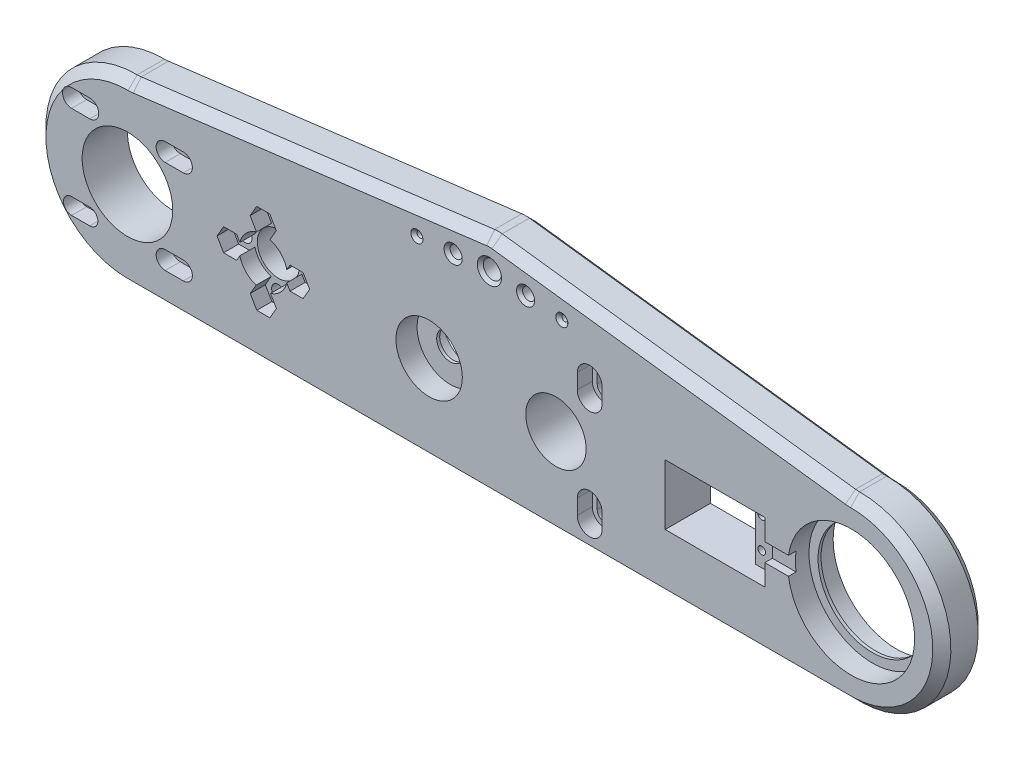
SolidWorks part; units mm, degrees
material "PLA+"
ref_plane "Front Plane" through (0, 0, 0) normal (0, 0, 1) x (1, 0, 0)
ref_plane "Top Plane" through (0, 0, 0) normal (0, 1, 0) x (1, 0, 0)
ref_plane "Right Plane" through (0, 0, 0) normal (1, 0, 0) x (0, 0, -1)
sketch "Sketch1" plane through (0, 0, 0) normal (0, 0, 1) x (1, 0, 0)
  line L2 (203.08, 10) -> (203.08, -10)
  line L6 (178.08, -10) -> (211.08, -10)
  line L7 (178.08, -10) -> (178.08, 10)
  line L8 (211.08, 10) -> (178.08, 10)
  line L11 (150.58, 20.5) -> (150.58, 15.5)
  line L12 (155.58, 15.5) -> (155.58, 20.5)
  line L13 (239.71, 0) -> (99.91, 0) construction
  line L17 (15.5, 15.5) -> (15.5, -15.5) construction
  line L18 (99.91, 0) -> (0, 0) construction
  line L19 (155.58, -15.5) -> (155.58, -20.5)
  line L20 (150.58, -20.5) -> (150.58, -15.5)
  line L22 (-15.5, -15.5) -> (15.5, -15.5) construction
  line L23 (-15.5, -15.5) -> (-15.5, 15.5) construction
  line L24 (-15.5, 15.5) -> (15.5, 15.5) construction
  line L25 (15.5, -15.5) -> (15.5, 15.5) construction
  line L26 (-15.5, -15.5) -> (15.5, 15.5) construction
  line L27 (-15.5, 15.5) -> (15.5, -15.5) construction
  line L29 (211.08, 10) -> (213.08, 10)
  line L30 (213.08, 10) -> (213.08, -10)
  line L31 (213.08, -10) -> (211.08, -10)
  line L34 (0.8664, 29.9878) -> (238.8536, 29.9878)
  line L35 (-1.0627, -29.9815) -> (240.7645, -29.9815)
  circle A0 centre (239.71, 0) radius 21
  circle A1 centre (99.91, 0) radius 11
  circle A2 centre (0, 0) radius 15
  arc A3 (0.8664, 29.9878) -> (-1.0627, -29.9815) centre (0, 0) ccw
  arc A4 (240.7645, -29.9815) -> (238.8536, 29.9878) centre (239.71, 0) ccw
  circle A6 centre (205.08, 5) radius 1.25
  circle A7 centre (205.08, -5) radius 1.25
  arc A13 (150.58, 15.5) -> (155.58, 15.5) centre (153.08, 15.5) ccw
  arc A14 (155.58, 20.5) -> (150.58, 20.5) centre (153.08, 20.5) ccw
  circle A15 centre (99.91, 0) radius 4
  circle A17 centre (-15.5, -15.5) radius 1.5
  circle A18 centre (-15.5, 15.5) radius 1.5
  circle A19 centre (45, -11) radius 2.25
  circle A20 centre (56, 0) radius 2.25
  circle A21 centre (34, 0) radius 2.25
  circle A22 centre (15.5, -15.5) radius 1.5
  circle A23 centre (15.5, 15.5) radius 1.5
  circle A24 centre (45, 11) radius 2.25
  circle A25 centre (45, 0) radius 7
  circle A26 centre (45, 0) radius 11 construction
  arc A28 (155.58, -20.5) -> (150.58, -20.5) centre (153.08, -20.5) cw
  arc A29 (150.58, -15.5) -> (155.58, -15.5) centre (153.08, -15.5) cw
  circle A30 centre (239.71, 0) radius 17
  circle A31 centre (0, 0) radius 11
  dimension "D5" = 3
  dimension "D6" = 14
  dimension "D7" = 22
  dimension "D8" = 2
  dimension "D10" = 8
  dimension "D11" = 22
  dimension "D12" = 2.5
  dimension "D14" = 8
  dimension "D20" = 4.5
  dimension "D24" = 42
  dimension "D25" = 30
  dimension "D30" = 15.5
  dimension "D32" = 4
  dimension "D33" = 4
  dimension "D34" = 30
  dimension "D35" = 22
  dimension "D3" = 31
  dimension "D4" = 31
  dimension "D9" = 45
  dimension "D13" = 5
  dimension "D17" = 33
  dimension "D18" = 20
  dimension "D21" = 10
  dimension "D22" = 5
  dimension "D26" = 99.91
  dimension "D27" = 139.8
  dimension "D36" = 31
sketch "Sketch2" plane through (0, 0, 0) normal (0, 0, 1) x (1, 0, 0)
  line L0 (178.08, -10) -> (211.08, -10) construction
  line L1 (178.08, -10) -> (178.08, 10) construction
  line L2 (211.08, -10) -> (211.08, 10) construction
  line L3 (211.08, 10) -> (178.08, 10) construction
  line L4 (150.58, -20.5) -> (150.58, -15.5) construction
  line L5 (155.58, -15.5) -> (155.58, -20.5) construction
  line L6 (150.58, 20.5) -> (150.58, 15.5) construction
  line L7 (155.58, 15.5) -> (155.58, 20.5) construction
  line L10 (178.08, -10) -> (211.08, -10)
  line L11 (178.08, -10) -> (178.08, 10)
  line L12 (211.08, -10) -> (211.08, 10)
  line L13 (211.08, 10) -> (178.08, 10)
  line L14 (150.58, -20.5) -> (150.58, -15.5)
  line L15 (155.58, -15.5) -> (155.58, -20.5)
  line L16 (150.58, 20.5) -> (150.58, 15.5)
  line L17 (155.58, 15.5) -> (155.58, 20.5)
  line L18 (238.8536, 29.9878) -> (0.8664, 29.9878)
  line L19 (-1.0627, -29.9815) -> (240.7645, -29.9815)
  line L21 (-18.5, 15.5) -> (-12.5, 15.5) construction
  line L22 (-18.5, 17.3) -> (-12.5, 17.3)
  line L23 (-18.5, 13.7) -> (-12.5, 13.7)
  line L24 (12.5, 15.5) -> (18.5, 15.5) construction
  line L25 (12.5, 17.3) -> (18.5, 17.3)
  line L26 (12.5, 13.7) -> (18.5, 13.7)
  line L27 (-18.5, -15.5) -> (-12.5, -15.5) construction
  line L28 (-18.5, -13.7) -> (-12.5, -13.7)
  line L29 (-18.5, -17.3) -> (-12.5, -17.3)
  line L30 (12.5, -15.5) -> (18.5, -15.5) construction
  line L31 (12.5, -13.7) -> (18.5, -13.7)
  line L32 (12.5, -17.3) -> (18.5, -17.3)
  arc A0 (240.7645, -29.9815) -> (238.8536, 29.9878) centre (239.71, 0) ccw construction
  circle A1 centre (239.71, 0) radius 21 construction
  arc A2 (150.58, -20.5) -> (155.58, -20.5) centre (153.08, -20.5) ccw construction
  arc A3 (155.58, -15.5) -> (150.58, -15.5) centre (153.08, -15.5) ccw construction
  arc A4 (-18.5, 17.3) -> (-18.5, 13.7) centre (-18.5, 15.5) ccw
  arc A5 (-12.5, 13.7) -> (-12.5, 17.3) centre (-12.5, 15.5) ccw
  arc A6 (12.5, 17.3) -> (12.5, 13.7) centre (12.5, 15.5) ccw
  arc A7 (155.58, 20.5) -> (150.58, 20.5) centre (153.08, 20.5) ccw construction
  arc A8 (150.58, 15.5) -> (155.58, 15.5) centre (153.08, 15.5) ccw construction
  circle A9 centre (99.91, 0) radius 11 construction
  circle A11 centre (45, 0) radius 7 construction
  arc A15 (0.8664, 29.9878) -> (-1.0627, -29.9815) centre (0, 0) ccw construction
  circle A16 centre (-15.5, -15.5) radius 1.5 construction
  circle A17 centre (15.5, -15.5) radius 1.5 construction
  circle A18 centre (15.5, 15.5) radius 1.5 construction
  circle A19 centre (-15.5, 15.5) radius 1.5 construction
  circle A20 centre (0, 0) radius 15 construction
  arc A21 (240.7645, -29.9815) -> (238.8536, 29.9878) centre (239.71, 0) ccw
  circle A22 centre (239.71, 0) radius 21
  arc A23 (150.58, -20.5) -> (155.58, -20.5) centre (153.08, -20.5) ccw
  arc A24 (155.58, -15.5) -> (150.58, -15.5) centre (153.08, -15.5) ccw
  arc A28 (155.58, 20.5) -> (150.58, 20.5) centre (153.08, 20.5) ccw
  arc A29 (150.58, 15.5) -> (155.58, 15.5) centre (153.08, 15.5) ccw
  circle A30 centre (99.91, 0) radius 11
  circle A32 centre (45, 0) radius 7
  arc A36 (0.8664, 29.9878) -> (-1.0627, -29.9815) centre (0, 0) ccw
  circle A41 centre (0, 0) radius 15
  arc A42 (18.5, 13.7) -> (18.5, 17.3) centre (18.5, 15.5) ccw
  arc A43 (-18.5, -13.7) -> (-18.5, -17.3) centre (-18.5, -15.5) ccw
  arc A44 (-12.5, -17.3) -> (-12.5, -13.7) centre (-12.5, -15.5) ccw
  arc A45 (12.5, -13.7) -> (12.5, -17.3) centre (12.5, -15.5) ccw
  arc A46 (18.5, -17.3) -> (18.5, -13.7) centre (18.5, -15.5) ccw
  point P9 (-15.5, 15.5)
  point P23 (-15.5, 15.5)
  point P28 (15.5, 15.5)
  point P74 (-15.5, -15.5)
  point P81 (15.5, -15.5)
  dimension "D1" = 1.8
  dimension "D2" = 1.8
  dimension "D3" = 1.8
  dimension "D4" = 1.8
  dimension "D5" = 6
  dimension "D6" = 6
  dimension "D7" = 6
  dimension "D8" = 6
extrude "Boss-Extrude1" add sketch "Sketch2" along normal mid plane 15
sketch "Sketch3" plane through (0, 0, 0) normal (0, 0, 1) x (1, 0, 0)
  circle A0 centre (99.91, 0) radius 11 construction
  circle A4 centre (0, 0) radius 15 construction
  circle A6 centre (99.91, 0) radius 11
  circle A10 centre (0, 0) radius 15
  circle A12 centre (240.08, 0) radius 18
  circle A14 centre (99.91, 0) radius 4.5
  circle A15 centre (240.08, 0) radius 21.5
  dimension "D1" = 36
  dimension "D2" = 9
extrude "Boss-Extrude2" add sketch "Sketch3" along normal mid plane 1
sketch "Sketch4" plane through (0, 0, 0) normal (0, 0, 1) x (1, 0, 0)
  line L0 (211.08, -10) -> (211.08, 10) construction
  line L1 (203.08, 10) -> (203.08, -10) construction
  line L2 (211.08, -10) -> (211.08, 10)
  line L3 (203.08, 10) -> (203.08, -10)
  line L4 (203.08, 10) -> (211.08, 10)
  line L5 (203.08, -10) -> (211.08, -10)
  circle A0 centre (205.08, -5) radius 1.25 construction
  circle A1 centre (205.08, 5) radius 1.25 construction
  circle A2 centre (205.08, -5) radius 1.25
  circle A3 centre (205.08, 5) radius 1.25
extrude "Boss-Extrude3" add sketch "Sketch4" along normal mid plane 5
sketch "Sketch5" plane through (0, 0, 0) normal (0, 0, 1) x (1, 0, 0)
  line L0 (0.8664, 29.9878) -> (119.86, 44.9878)
  line L1 (119.86, 44.9878) -> (238.8536, 29.9878)
  line L2 (238.8536, 29.9878) -> (0.8664, 29.9878)
  line L3 (119.86, 30.9878) -> (95.86, 30.9878) construction
  line L4 (119.86, 44.9878) -> (119.86, 34.9878) construction
  circle A0 centre (119.86, 34.9878) radius 4
  circle A1 centre (107.86, 33.9878) radius 3
  circle A2 centre (95.86, 32.9878) radius 2
  circle A5 centre (131.86, 33.9878) radius 3
  circle A6 centre (143.86, 32.9878) radius 2
  point P18 (119.86, 29.9878)
  dimension "D2" = 8
  dimension "D3" = 6
  dimension "D4" = 4
  dimension "D1" = 15
  dimension "D5" = 12
  dimension "D6" = 12
  dimension "D7" = 10
extrude "Boss-Extrude6" add sketch "Sketch5" along normal mid plane 15 contours L2 L0 L1
fillet "Fillet1" radius 10 3 edges at (238.8536, 29.9878, 0) (0.8664, 29.9878, 0) (119.86, 44.9878, 0)
sketch "Sketch6" plane through (0, 0, 7.5) normal (0, 0, 1) x (1, 0, 0)
  circle A0 centre (131.86, 33.9878) radius 3 construction
  circle A1 centre (131.86, 33.9878) radius 3
  circle A2 centre (143.86, 32.9878) radius 2 construction
  circle A3 centre (143.86, 32.9878) radius 2
  circle A4 centre (95.86, 32.9878) radius 2 construction
  circle A15 centre (107.86, 33.9878) radius 3 construction
  circle A16 centre (119.86, 34.9878) radius 4 construction
  circle A17 centre (95.86, 32.9878) radius 2
  circle A18 centre (107.86, 33.9878) radius 3
  circle A19 centre (119.86, 34.9878) radius 4
extrude "Cut-Extrude2" cut sketch "Sketch6" against normal blind 1
chamfer "Chamfer1" distance 1 angle 45 5 edges at (145.86, 32.9878, 6.5) (134.86, 33.9878, 6.5) (123.86, 34.9878, 6.5) (110.86, 33.9878, 6.5) (97.86, 32.9878, 6.5)
chamfer "Chamfer2" distance 3 angle 45 16 edges at (119.8509, -29.9815, -7.5) (-29.9932, 0.6541, -7.5) (0.913, 30.0161, -7.5) (60.0936, 37.4538, -7.5) (119.86, 44.9086, -7.5) (179.6271, 37.4537, -7.5) (238.8071, 30.016, -7.5) (269.7031, 0.6457, -7.5) (238.8071, 30.016, 7.5) (269.7031, 0.6457, 7.5) (119.8509, -29.9815, 7.5) (-29.9932, 0.6541, 7.5) (0.913, 30.0161, 7.5) (179.6271, 37.4537, 7.5) (119.86, 44.9086, 7.5) (60.0936, 37.4538, 7.5)
mirror "Mirror1" about plane through (0, 0, 0) normal (0, 0, 1) of "Chamfer1", "Cut-Extrude2"
sketch "Sketch7" plane through (0, 0, 7.5) normal (0, 0, 1) x (1, 0, 0)
  circle A0 centre (119.86, 34.9878) radius 3
  circle A1 centre (131.86, 33.9878) radius 2
  circle A2 centre (107.86, 33.9878) radius 2
  circle A3 centre (143.86, 32.9878) radius 1
  circle A4 centre (95.86, 32.9878) radius 1
extrude "Cut-Extrude3" cut sketch "Sketch7" against normal through all
sketch "Sketch9" plane through (0, 0, 7.5) normal (0, 0, 1) x (1, 0, 0)
  line L0 (-18.5, 17.3) -> (-12.5, 17.3)
  line L1 (-18.5, 13.7) -> (-12.5, 13.7)
  line L2 (-18.5, -14) -> (-12.5, -14)
  line L3 (-18.5, -17) -> (-12.5, -17)
  line L8 (12.5, 17.3) -> (18.5, 17.3)
  line L9 (12.5, 13.7) -> (18.5, 13.7)
  line L10 (12.5, -13.7) -> (18.5, -13.7)
  line L11 (12.5, -17.3) -> (18.5, -17.3)
  line L12 (12.5, 12.5) -> (18.5, 12.5)
  line L13 (12.5, 18.5) -> (18.5, 18.5)
  line L14 (-18.5, 18.5) -> (-12.5, 18.5)
  line L15 (-18.5, 12.5) -> (-12.5, 12.5)
  line L16 (-18.5, -12.8) -> (-12.5, -12.8)
  line L17 (-18.5, -18.2) -> (-12.5, -18.2)
  line L18 (12.5, -12.5) -> (18.5, -12.5)
  line L19 (12.5, -18.5) -> (18.5, -18.5)
  arc A0 (-18.5, 17.3) -> (-18.5, 13.7) centre (-18.5, 15.5) ccw
  arc A1 (-12.5, 13.7) -> (-12.5, 17.3) centre (-12.5, 15.5) ccw
  arc A2 (-18.5, -14) -> (-18.5, -17) centre (-18.5, -15.5) ccw
  arc A3 (-12.5, -17) -> (-12.5, -14) centre (-12.5, -15.5) ccw
  arc A8 (12.5, 17.3) -> (12.5, 13.7) centre (12.5, 15.5) ccw
  arc A9 (18.5, 13.7) -> (18.5, 17.3) centre (18.5, 15.5) ccw
  arc A10 (12.5, -13.7) -> (12.5, -17.3) centre (12.5, -15.5) ccw
  arc A11 (18.5, -17.3) -> (18.5, -13.7) centre (18.5, -15.5) ccw
  arc A12 (18.5, 12.5) -> (18.5, 18.5) centre (18.5, 15.5) ccw
  arc A13 (12.5, 18.5) -> (12.5, 12.5) centre (12.5, 15.5) ccw
  arc A14 (-12.5, 12.5) -> (-12.5, 18.5) centre (-12.5, 15.5) ccw
  arc A15 (-18.5, 18.5) -> (-18.5, 12.5) centre (-18.5, 15.5) ccw
  arc A16 (-12.5, -18.2) -> (-12.5, -12.8) centre (-12.5, -15.5) ccw
  arc A17 (-18.5, -12.8) -> (-18.5, -18.2) centre (-18.5, -15.5) ccw
  arc A18 (18.5, -18.5) -> (18.5, -12.5) centre (18.5, -15.5) ccw
  arc A19 (12.5, -12.5) -> (12.5, -18.5) centre (12.5, -15.5) ccw
  dimension "D1" = 1.2
  dimension "D2" = 1.2
  dimension "D3" = 1.2
  dimension "D4" = 1.2
extrude "Cut-Extrude8" cut sketch "Sketch9" against normal blind 5
sketch "Sketch11" plane through (0, 0, 7.5) normal (0, 0, 1) x (1, 0, 0)
  line L7 (148.98, -15.5) -> (148.98, -20.5)
  line L8 (157.18, -20.5) -> (157.18, -15.5)
  line L9 (148.98, -15.5) -> (148.98, -20.5)
  line L10 (157.18, -20.5) -> (157.18, -15.5)
  line L14 (148.98, 20.5) -> (148.98, 15.5)
  line L15 (157.18, 15.5) -> (157.18, 20.5)
  line L16 (148.98, 20.5) -> (148.98, 15.5)
  line L17 (157.18, 15.5) -> (157.18, 20.5)
  arc A6 (148.98, -20.5) -> (157.18, -20.5) centre (153.08, -20.5) ccw
  arc A7 (157.18, -15.5) -> (148.98, -15.5) centre (153.08, -15.5) ccw
  arc A8 (148.98, -20.5) -> (157.18, -20.5) centre (153.08, -20.5) ccw
  arc A9 (157.18, -15.5) -> (148.98, -15.5) centre (153.08, -15.5) ccw
  arc A16 (148.98, 15.5) -> (157.18, 15.5) centre (153.08, 15.5) ccw
  arc A17 (157.18, 20.5) -> (148.98, 20.5) centre (153.08, 20.5) ccw
  arc A18 (148.98, 15.5) -> (157.18, 15.5) centre (153.08, 15.5) ccw
  arc A19 (157.18, 20.5) -> (148.98, 20.5) centre (153.08, 20.5) ccw
  dimension "D1" = 1.6
  dimension "D2" = 1.6
extrude "Cut-Extrude11" cut sketch "Sketch11" against normal blind 5
sketch "Sketch13" plane through (0, 0, 7.5) normal (0, 0, 1) x (1, 0, 0)
  line L0 (99.91, 0) -> (141.91, 0) construction
  circle A0 centre (141.91, 0) radius 10
  dimension "D2" = 20
  dimension "D1" = 42
extrude "Cut-Extrude12" cut sketch "Sketch13" against normal through all
sketch "Sketch14" plane through (0, 0, -7.5) normal (0, 0, -1) x (-1, 0, 0)
  line L0 (-18.5, 17.3) -> (-12.5, 17.3)
  line L1 (-18.5, 13.7) -> (-12.5, 13.7)
  line L2 (12.5, 17.3) -> (18.5, 17.3)
  line L3 (12.5, 13.7) -> (18.5, 13.7)
  line L4 (-18.5, -13.7) -> (-12.5, -13.7)
  line L5 (-18.5, -17.3) -> (-12.5, -17.3)
  line L6 (12.5, -13.7) -> (18.5, -13.7)
  line L7 (12.5, -17.3) -> (18.5, -17.3)
  line L8 (-18.5, 12.5) -> (-12.5, 12.5)
  line L9 (-18.5, 18.5) -> (-12.5, 18.5)
  line L10 (12.5, 12.5) -> (18.5, 12.5)
  line L11 (12.5, 18.5) -> (18.5, 18.5)
  line L12 (-18.5, -12.5) -> (-12.5, -12.5)
  line L13 (-18.5, -18.5) -> (-12.5, -18.5)
  line L14 (12.5, -18.5) -> (18.5, -18.5)
  line L15 (12.5, -12.5) -> (18.5, -12.5)
  arc A0 (-18.5, 17.3) -> (-18.5, 13.7) centre (-18.5, 15.5) ccw
  arc A1 (-12.5, 13.7) -> (-12.5, 17.3) centre (-12.5, 15.5) ccw
  arc A2 (12.5, 17.3) -> (12.5, 13.7) centre (12.5, 15.5) ccw
  arc A3 (18.5, 13.7) -> (18.5, 17.3) centre (18.5, 15.5) ccw
  arc A4 (-18.5, -13.7) -> (-18.5, -17.3) centre (-18.5, -15.5) ccw
  arc A5 (-12.5, -17.3) -> (-12.5, -13.7) centre (-12.5, -15.5) ccw
  arc A6 (12.5, -13.7) -> (12.5, -17.3) centre (12.5, -15.5) ccw
  arc A7 (18.5, -17.3) -> (18.5, -13.7) centre (18.5, -15.5) ccw
  arc A8 (-18.5, 18.5) -> (-18.5, 12.5) centre (-18.5, 15.5) ccw
  arc A9 (-12.5, 12.5) -> (-12.5, 18.5) centre (-12.5, 15.5) ccw
  arc A10 (12.5, 18.5) -> (12.5, 12.5) centre (12.5, 15.5) ccw
  arc A11 (18.5, 12.5) -> (18.5, 18.5) centre (18.5, 15.5) ccw
  arc A12 (-12.5, -18.5) -> (-12.5, -12.5) centre (-12.5, -15.5) ccw
  arc A13 (-18.5, -12.5) -> (-18.5, -18.5) centre (-18.5, -15.5) ccw
  arc A14 (12.5, -12.5) -> (12.5, -18.5) centre (12.5, -15.5) ccw
  arc A15 (18.5, -18.5) -> (18.5, -12.5) centre (18.5, -15.5) ccw
  dimension "D1" = 1.2
extrude "Cut-Extrude13" cut sketch "Sketch14" against normal blind 5
sketch "Sketch15" plane through (0, 0, 7.5) normal (0, 0, 1) x (1, 0, 0)
  circle A0 centre (0, 0) radius 15
extrude "Cut-Extrude14" cut sketch "Sketch15" against normal through all
sketch "Sketch16" plane through (0, 0, -7.5) normal (0, 0, -1) x (-1, 0, 0)
  line L17 (-148.98, 15.5) -> (-148.98, 20.5)
  line L20 (-148.98, -20.5) -> (-148.98, -15.5)
  line L21 (-157.18, -15.5) -> (-157.18, -20.5)
  line L22 (-148.98, -20.5) -> (-148.98, -15.5)
  line L23 (-157.18, -15.5) -> (-157.18, -20.5)
  line L25 (-157.18, 20.5) -> (-157.18, 15.5)
  line L26 (-148.98, 15.5) -> (-148.98, 20.5)
  line L27 (-157.18, 20.5) -> (-157.18, 15.5)
  arc A11 (-157.18, 15.5) -> (-148.98, 15.5) centre (-153.08, 15.5) ccw
  arc A12 (-148.98, 20.5) -> (-157.18, 20.5) centre (-153.08, 20.5) ccw
  arc A15 (-157.18, 15.5) -> (-148.98, 15.5) centre (-153.08, 15.5) ccw
  arc A16 (-148.98, 20.5) -> (-157.18, 20.5) centre (-153.08, 20.5) ccw
  arc A29 (-157.18, -20.5) -> (-148.98, -20.5) centre (-153.08, -20.5) ccw
  arc A30 (-148.98, -15.5) -> (-157.18, -15.5) centre (-153.08, -15.5) ccw
  arc A31 (-157.18, -20.5) -> (-148.98, -20.5) centre (-153.08, -20.5) ccw
  arc A32 (-148.98, -15.5) -> (-157.18, -15.5) centre (-153.08, -15.5) ccw
  dimension "D1" = 1.6
  dimension "D2" = 1.6
extrude "Cut-Extrude15" cut sketch "Sketch16" against normal blind 5
sketch "Sketch17" plane through (0, 0, 7.5) normal (0, 0, 1) x (1, 0, 0)
  line L0 (211.08, -10) -> (211.08, 10) construction
  line L1 (211.08, 3) -> (220.08, 3)
  line L2 (211.08, 3) -> (211.08, -3)
  line L3 (211.08, -3) -> (220.08, -3)
  line L4 (220.08, 3) -> (220.08, -3)
  line L5 (178.08, 0) -> (230.079, 0) construction
  line L6 (178.08, 10) -> (178.08, -10) construction
  circle A0 centre (239.71, 0) radius 21 construction
  circle A1 centre (239.71, 0) radius 21 construction
  dimension "D1" = 6
  dimension "D2" = 3
  dimension "D3" = 9
extrude "Cut-Extrude16" cut sketch "Sketch17" against normal blind 2.5
sketch "Sketch18" plane through (0, 0, -7.5) normal (0, 0, -1) x (-1, 0, 0)
  line L0 (0, 0) -> (-18.8, 0) construction
  circle A0 centre (-18.8, 0) radius 2.59
  dimension "D2" = 5.18
  dimension "D1" = 18.8
extrude "Cut-Extrude17" cut sketch "Sketch18" against normal blind 3
sketch "Sketch19" plane through (0, 0, 7.5) normal (0, 0, 1) x (1, 0, 0)
  line L0 (-1.0081, -26.9815) -> (240.7104, -26.9815) construction
  line L1 (47.2039, 7.6904) -> (49.2919, 11.307)
  line L2 (49.2919, 11.307) -> (47.1268, 15.057)
  line L3 (47.1268, 15.057) -> (42.7967, 15.057)
  line L4 (42.7967, 15.057) -> (40.6317, 11.307)
  line L5 (40.6317, 11.307) -> (42.7307, 7.6714)
  line L7 (47.1651, -14.75) -> (49.3301, -11)
  line L8 (49.3301, -11) -> (47.3876, -7.6354)
  line L10 (42.6124, -7.6354) -> (40.6699, -11)
  line L11 (40.6699, -11) -> (42.8349, -14.75)
  line L12 (42.8349, -14.75) -> (47.1651, -14.75)
  line L13 (58.1651, -3.75) -> (60.3301, 0)
  line L14 (60.3301, 0) -> (58.1651, 3.75)
  line L15 (58.1651, 3.75) -> (53.8349, 3.75)
  line L16 (53.8349, 3.75) -> (52.7524, 1.875)
  line L17 (52.7524, -1.875) -> (53.8349, -3.75)
  line L18 (53.8349, -3.75) -> (58.1651, -3.75)
  line L19 (36.1651, -3.75) -> (37.2476, -1.875)
  line L20 (37.2476, 1.875) -> (36.1651, 3.75)
  line L21 (36.1651, 3.75) -> (31.8349, 3.75)
  line L22 (31.8349, 3.75) -> (29.6699, 0)
  line L23 (29.6699, 0) -> (31.8349, -3.75)
  line L24 (31.8349, -3.75) -> (36.1651, -3.75)
  line L25 (42.7967, 7.557) -> (44.9618, 7.557) [skipped]
  line L26 (47.1651, -7.25) -> (45, -7.25) [skipped]
  circle A0 centre (44.9618, 11.307) radius 3.75 construction
  circle A1 centre (45, -11) radius 3.75 construction
  arc A2 (52.7524, -1.875) -> (52.7524, 1.875) centre (56, 0) ccw construction
  arc A3 (37.2476, 1.875) -> (37.2476, -1.875) centre (34, 0) ccw construction
  circle A4 centre (45, 0) radius 8
  dimension "D5" = 16
  dimension "D2" = 7.5
  dimension "D3" = 7.5
extrude "Cut-Extrude18" cut sketch "Sketch19" against normal blind 5 contours A4 L1 L2 L3 L4 L5 | A4 L17 L18 L13 L14 L15 L16 | A4 L20 L21 L22 L23 L24 L19 | A4 L10 L11 L12 L7 L8 | A4 region at (44.961, 11.4204, 7.5) region at (45, 0, 7.5) region at (56.2037, 0, 7.5) region at (33.7963, 0, 7.5) region at (45, -11.2181, 7.5)
sketch "Sketch21" plane through (0, 0, -7.5) normal (0, 0, -1) x (-1, 0, 0)
  circle A0 centre (-45, 0) radius 11 construction
  circle A1 centre (-45, 11) radius 2.25
  circle A2 centre (-34, 0) radius 2.25
  circle A3 centre (-56, 0) radius 2.25
  circle A4 centre (-45, -11) radius 2.25
  dimension "D1" = 22
  dimension "D2" = 4.5
  dimension "D3" = 4.5
  dimension "D4" = 4.5
  dimension "D5" = 4.5
extrude "Cut-Extrude19" cut sketch "Sketch21" against normal through all
sketch "Sketch22" plane through (0, 0, -7.5) normal (0, 0, -1) x (-1, 0, 0)
  circle A0 centre (-45, 11) radius 3.9
  circle A1 centre (-34, 0) radius 3.9
  circle A2 centre (-45, -11) radius 3.9
  circle A3 centre (-56, 0) radius 3.9
  dimension "D1" = 7.8
  dimension "D2" = 7.8
  dimension "D3" = 7.8
  dimension "D4" = 7.8
extrude "Cut-Extrude20" cut sketch "Sketch22" against normal blind 5.5
sketch "Sketch26" plane through (0, 0, 7.5) normal (0, 0, 1) x (1, 0, 0)
  circle A4 centre (239.71, 0) radius 21
extrude "Boss-Extrude8" add sketch "Sketch26" against normal blind 15
sketch "Sketch27" plane through (0, 0, 7.5) normal (0, 0, 1) x (1, 0, 0)
  circle A0 centre (239.71, 0) radius 18
  dimension "D1" = 36
extrude "Cut-Extrude21" cut sketch "Sketch27" against normal through all
sketch "Sketch28" plane through (0, 0, 7.5) normal (0, 0, 1) x (1, 0, 0)
  circle A0 centre (239.71, 0) radius 21
  dimension "D1" = 42
extrude "Cut-Extrude22" cut sketch "Sketch28" against normal blind 7
sketch "Sketch29" plane through (0, 0, -7.5) normal (0, 0, -1) x (-1, 0, 0)
  circle A0 centre (-239.71, 0) radius 21
  dimension "D1" = 42
extrude "Cut-Extrude23" cut sketch "Sketch29" against normal blind 7
